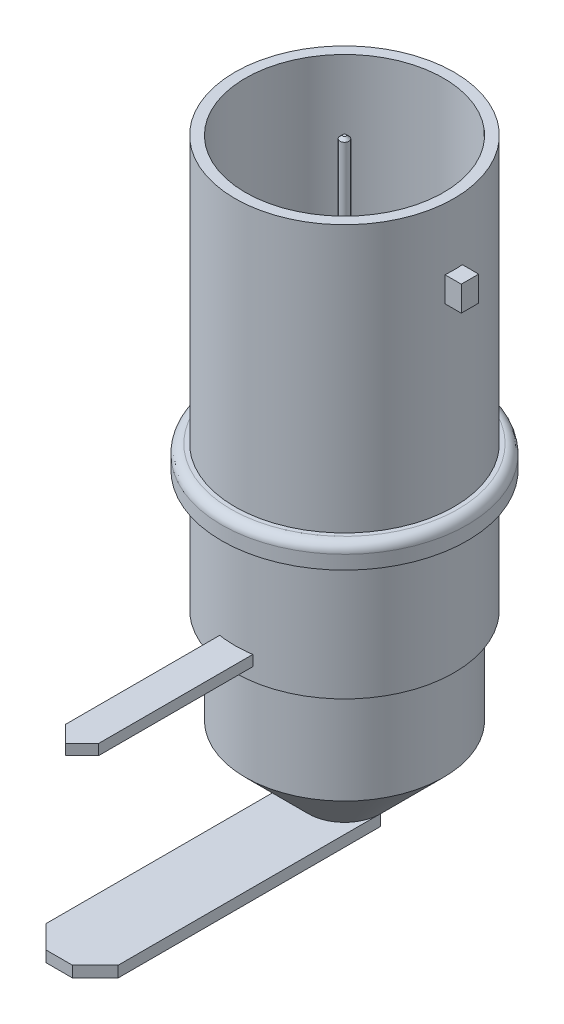
SolidWorks part; units mm, degrees
ref_plane "Front Plane" through (0, 0, 0) normal (0, 0, 1) x (1, 0, 0)
ref_plane "Top Plane" through (0, 0, 0) normal (0, 1, 0) x (1, 0, 0)
ref_plane "Right Plane" through (0, 0, 0) normal (1, 0, 0) x (0, 0, -1)
sketch "Sketch1" plane through (0, 0, 0) normal (0, 1, 0) x (1, 0, 0)
  circle A0 centre (0, 0) radius 4.8
  circle A1 centre (0, 0) radius 4.3415
  dimension "D1" = 9.6
extrude "Boss-Extrude1" add sketch "Sketch1" along normal blind 18
ref_plane "Plane1" through (0, 18, 0) normal (0, 1, 0) x (1, 0, 0)
ref_plane "Plane2" through (0, 5.3, 0) normal (0, 1, 0) x (1, 0, 0)
sketch "Sketch2" plane through (0, 5.3, 0) normal (0, 1, 0) x (1, 0, 0)
  circle A0 centre (0, 0) radius 5.3801
  circle A1 centre (0, 0) radius 4.8
extrude "Boss-Extrude2" add sketch "Sketch2" along normal blind 1
fillet "Fillet1" radius 0.4 1 edges at (0, 6.3, 5.3801)
sketch "Sketch3" plane through (0, 0, 0) normal (0, 0, 1) x (1, 0, 0)
  line L0 (0, 0) -> (0, 18) construction
  line L1 (4.7756, 18) -> (-4.7756, 18) construction
  line L2 (-4.6139, 15.2917) -> (-5.5, 15.2917)
  line L4 (-5.5, 15.2917) -> (-5.5, 14.1904)
  line L5 (-5.5, 14.1904) -> (-4.6139, 14.1904)
  line L6 (-4.6139, 14.1904) -> (-4.6139, 15.2917)
  line L7 (4.6139, 14.1904) -> (4.6139, 15.2917)
  line L8 (5.5, 14.1904) -> (4.6139, 14.1904)
  line L9 (5.5, 15.2917) -> (5.5, 14.1904)
  line L10 (4.6139, 15.2917) -> (5.5, 15.2917)
  dimension "D1" = 5.5
extrude "Boss-Extrude3" add sketch "Sketch3" along normal mid plane 0.762
sketch "Sketch4" plane through (0, 5.3, 0) normal (0, 1, 0) x (1, 0, 0)
  circle A0 centre (0, 0) radius 0.1949
extrude "Boss-Extrude4" add sketch "Sketch4" along normal up to surface (12.7 mm away) separate body up to face at (0, 18, 4.8)
chamfer "Chamfer1" distance 0.127 angle 45 1 edges at (0, 18, 0.1949)
sketch "Sketch6" plane through (0, 0, 0) normal (0, 0, 1) x (1, 0, 0)
  line L0 (0, 5.3) -> (0, -4.3192) construction
  line L1 (4.7756, 5.3) -> (-4.7756, 5.3) construction
  line L3 (-0.725, 0.5681) -> (0.725, 0.5681)
  line L4 (-0.725, 0.5681) -> (-0.725, 1.0319)
  line L5 (-0.725, 1.0319) -> (0.725, 1.0319)
  line L6 (0.725, 0.5681) -> (0.725, 1.0319)
  line L7 (-0.725, 0.5681) -> (0.725, 1.0319) construction
  line L8 (-0.725, 1.0319) -> (0.725, 0.5681) construction
  line L9 (-1.58, -7.4425) -> (1.58, -7.4425)
  line L10 (-1.58, -7.4425) -> (-1.58, -6.9575)
  line L11 (-1.58, -6.9575) -> (1.58, -6.9575)
  line L12 (1.58, -7.4425) -> (1.58, -6.9575)
  line L13 (-1.58, -7.4425) -> (1.58, -6.9575) construction
  line L14 (-1.58, -6.9575) -> (1.58, -7.4425) construction
  point P5 (0, 0.8)
  point P10 (0, -7.2)
  dimension "D1" = 12.5
  dimension "D2" = 3.16
  dimension "D3" = 1.45
  dimension "D4" = 4.5
extrude "Boss-Extrude5" add sketch "Sketch6" along normal blind 12.5 separate body
chamfer "Chamfer2" distance 1 angle 45 2 edges at (-0.725, 0.8, 12.5) (0.725, 0.8, 12.5)
chamfer "Chamfer3" distance 1 angle 45 2 edges at (1.58, -7.2, 12.5) (-1.58, -7.2, 12.5)
sketch "Sketch7" plane through (0, 5.3, 0) normal (0, 1, 0) x (1, 0, 0)
  circle A0 centre (0, 0) radius 4.3415
extrude "Boss-Extrude6" add sketch "Sketch7" along normal blind 4 and the other way blind 12.5 separate body
chamfer "Chamfer4" distance 3 angle 45 1 edges at (0, -7.2, 4.3415)
